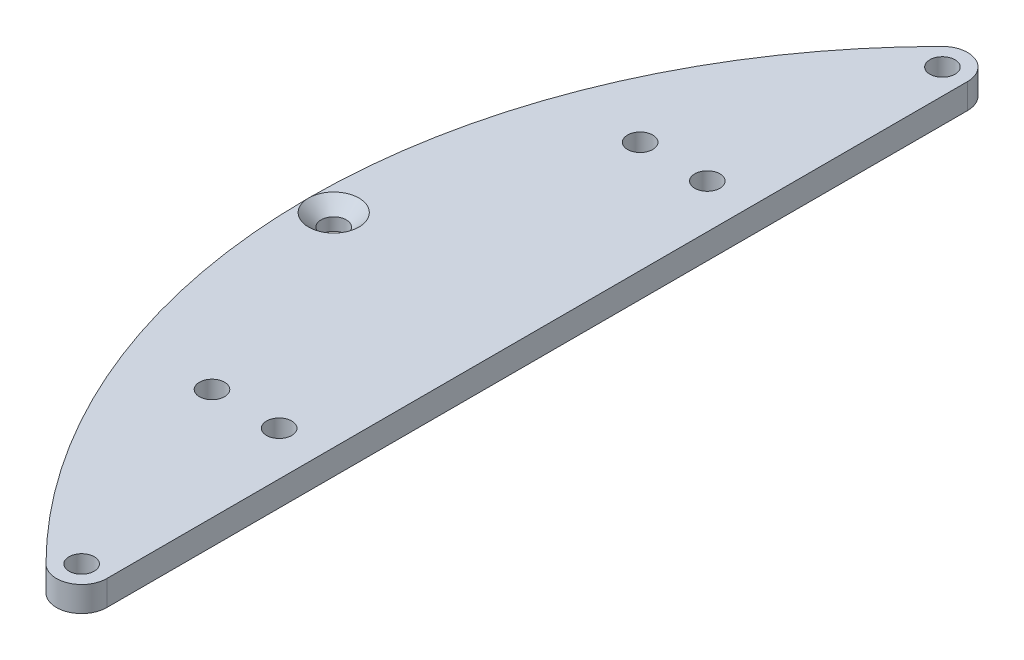
SolidWorks part; units mm, degrees
material "碳板"
ref_plane "前视基准面" through (0, 0, 0) normal (0, 0, 1) x (1, 0, 0)
ref_plane "上视基准面" through (0, 0, 0) normal (0, 1, 0) x (1, 0, 0)
ref_plane "右视基准面" through (0, 0, 0) normal (1, 0, 0) x (0, 0, -1)
sketch "草图1" plane through (0, 0, 0) normal (0, 1, 0) x (1, 0, 0)
  line L0 (0, 84.9919) -> (0, -83.5638) construction
  line L1 (-109.0577, 0) -> (112.8253, 0) construction
  line L2 (-48.2652, 51.2652) -> (-48.2652, -51.2652)
  circle A0 centre (0, 0) radius 72.5 construction
  circle A1 centre (0, 72.5) radius 1.5 construction
  circle A2 centre (51.2652, 51.2652) radius 1.5 construction
  circle A3 centre (72.5, 0) radius 1.5 construction
  circle A4 centre (51.2652, -51.2652) radius 1.5 construction
  circle A5 centre (0, -72.5) radius 1.5 construction
  circle A6 centre (-51.2652, -51.2652) radius 1.5
  circle A7 centre (-72.5, 0) radius 1.5
  circle A8 centre (-51.2652, 51.2652) radius 1.5
  arc A9 (-53.3866, 53.3866) -> (-53.3866, -53.3866) centre (0, 0) ccw
  arc A10 (-48.2652, 51.2652) -> (-53.3866, 53.3866) centre (-51.2652, 51.2652) ccw
  arc A11 (-48.2652, -51.2652) -> (-53.3866, -53.3866) centre (-51.2652, -51.2652) cw
  circle A86 centre (-53.5, -25.5) radius 1.25 construction
  circle A87 centre (-53.5, -25.5) radius 1.25
  circle A88 centre (-61.5, -25.5) radius 1.25 construction
  circle A89 centre (-61.5, -25.5) radius 1.25
  circle A90 centre (-61.5, 25.5) radius 1.25 construction
  circle A91 centre (-61.5, 25.5) radius 1.25
  circle A92 centre (-53.5, 25.5) radius 1.25 construction
  circle A93 centre (-53.5, 25.5) radius 1.25
  circle A106 centre (-61.5, -25.5) radius 1.5
  circle A107 centre (-53.5, -25.5) radius 1.5
  circle A108 centre (-61.5, 25.5) radius 1.5
  circle A109 centre (-53.5, 25.5) radius 1.5
  point P25 (0, 0)
  dimension "D1" = 145
  dimension "D2" = 3
  dimension "D4" = 151
  dimension "D5" = 3
  dimension "D3" = 8
extrude "凸台-拉伸1" add sketch "草图1" along normal blind 3 contours A11 L2 A10 A9 region at (-59.4766, 0, 0)
chamfer "倒角1" distance 1.5 angle 45 1 edges at (-72.5, 3, 1.5)
move or copy body "实体-移动/复制1" [suppressed] bodies to move or copy 106
